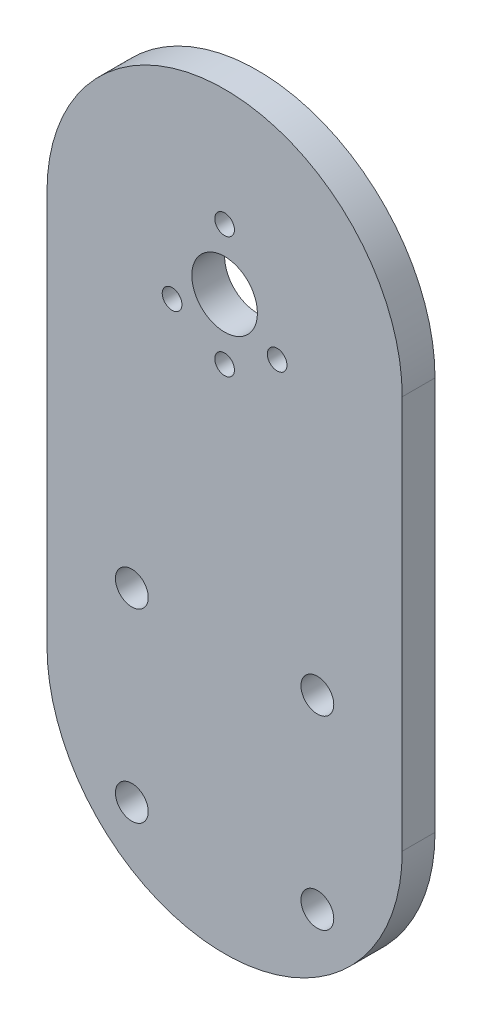
SolidWorks part; units mm, degrees
ref_plane "Front Plane" through (0, 0, 0) normal (0, 0, 1) x (1, 0, 0)
ref_plane "Top Plane" through (0, 0, 0) normal (0, 1, 0) x (1, 0, 0)
ref_plane "Right Plane" through (0, 0, 0) normal (1, 0, 0) x (0, 0, -1)
sketch "Sketch1" plane through (0, 0, 0) normal (0, 0, 1) x (1, 0, 0)
  line L0 (-27.08, 0) -> (-27.08, 60)
  line L2 (27.08, 60) -> (27.08, 0)
  arc A0 (-27.08, 0) -> (27.08, 0) centre (0, 0) ccw
  arc A1 (-27.08, 60) -> (27.08, 60) centre (0, 60) cw
  dimension "D1" = 27.08
  dimension "D2" = 60
extrude "Boss-Extrude1" add sketch "Sketch1" along normal blind 5
sketch "Sketch2" plane through (0, 0, 5) normal (0, 0, 1) x (1, 0, 0)
  line L0 (0, 0) -> (0, 20) construction
  line L1 (0, 0) -> (14.1421, 14.1421) construction
  circle A0 centre (0, 0) radius 20 construction
  circle A1 centre (14.1421, 14.1421) radius 2.5
  circle A2 centre (14.1421, -14.1421) radius 2.5
  circle A3 centre (-14.1421, -14.1421) radius 2.5
  circle A4 centre (-14.1421, 14.1421) radius 2.5
  point P15 (0, 0)
  dimension "D1" = 40
  dimension "D2" = 5
  dimension "D3" = 45
  dimension "D4" = 4
extrude "Cut-Extrude1" cut sketch "Sketch2" against normal blind 5
sketch "Sketch3" plane through (0, 0, 5) normal (0, 0, 1) x (1, 0, 0)
  circle A0 centre (0, 60) radius 5
  point P2 (0, 0)
  dimension "D2" = 10
  dimension "D1" = 60
extrude "Cut-Extrude2" cut sketch "Sketch3" against normal blind 5
sketch "Sketch4" plane through (0, 0, 5) normal (0, 0, 1) x (1, 0, 0)
  line L0 (-8.0107, 55.375) -> (0, 60) construction
  line L1 (0, 60) -> (8.0107, 55.375) construction
  line L2 (0, 50.75) -> (0, 60) construction
  circle A0 centre (0, 60) radius 9.25 construction
  circle A1 centre (0, 69.25) radius 1.5
  circle A2 centre (0, 50.75) radius 1.5
  circle A3 centre (8.0107, 55.375) radius 1.5
  circle A4 centre (-8.0107, 55.375) radius 1.5
  dimension "D1" = 18.5
  dimension "D2" = 3
  dimension "D3" = 60
  dimension "D4" = 60
extrude "Cut-Extrude3" cut sketch "Sketch4" against normal blind 5
